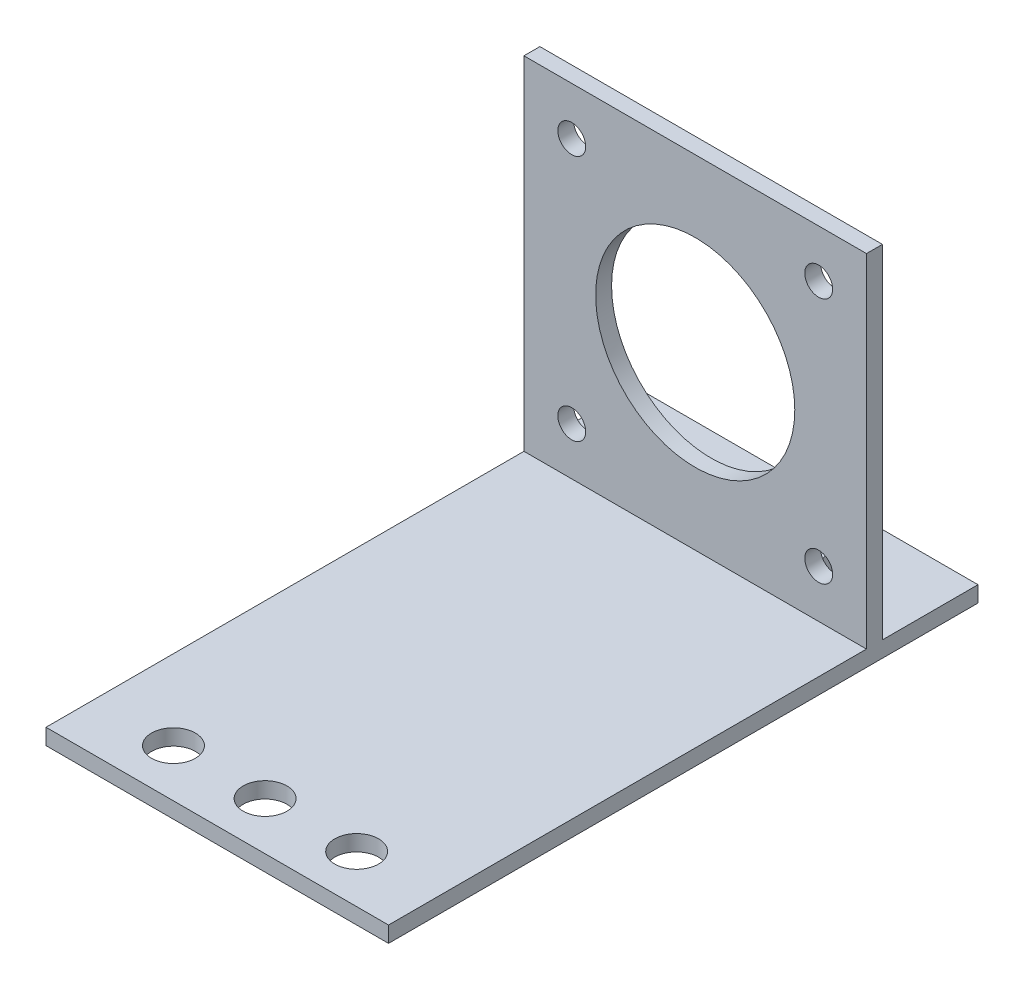
SolidWorks part; units mm, degrees
ref_plane "Front Plane" through (0, 0, 0) normal (0, 0, 1) x (1, 0, 0)
ref_plane "Top Plane" through (0, 0, 0) normal (0, 1, 0) x (1, 0, 0)
ref_plane "Right Plane" through (0, 0, 0) normal (1, 0, 0) x (0, 0, -1)
sketch "Sketch1" plane through (0, 0, 0) normal (0, 1, 0) x (1, 0, 0)
  line L0 (-21.5, 25) -> (21.5, 25)
  line L1 (-21.5, -37) -> (21.5, -37)
  line L2 (-21.5, -37) -> (-21.5, 37)
  line L3 (-21.5, 37) -> (21.5, 37)
  line L4 (21.5, -37) -> (21.5, 37)
  line L5 (-21.5, -37) -> (21.5, 37) construction
  line L6 (-21.5, 37) -> (21.5, -37) construction
  line L7 (-21.5, 23) -> (21.5, 23)
  line L8 (21.5, -25) -> (-21.5, -25) construction
  line L9 (0, 37) -> (0, -37) construction
  circle A0 centre (0, 31) radius 2.75
  circle A1 centre (0, -31) radius 2.75
  point P0 (0, 0)
  dimension "D6" = 6
  dimension "D7" = 5.5
  dimension "D8" = 5.5
  dimension "D9" = 6
  dimension "D1" = 12
  dimension "D2" = 2
  dimension "D3" = 43
  dimension "D4" = 48
  dimension "D5" = 12
extrude "Boss-Extrude1" add sketch "Sketch1" along normal blind 43 contours L2 L7 L4 L0 region at (0, 0, -24)
extrude "Boss-Extrude2" add sketch "Sketch1<3>" against normal blind 2 contours L4 L3 L2 L1
sketch "Sketch1<3>" plane through (0, 0, 0) normal (0, 1, 0) x (1, 0, 0) same geometry as "Sketch1"
sketch "Sketch2" plane through (0, 0, -23) normal (0, 0, 1) x (1, 0, 0)
  line L0 (-21.5, 43) -> (21.5, 43) construction
  line L1 (-15.5, 6) -> (15.5, 6) construction
  line L2 (-15.5, 6) -> (-15.5, 37) construction
  line L3 (-15.5, 37) -> (15.5, 37) construction
  line L4 (15.5, 6) -> (15.5, 37) construction
  line L5 (-15.5, 6) -> (15.5, 37) construction
  line L6 (-15.5, 37) -> (15.5, 6) construction
  line L7 (-21.5, 43) -> (-21.5, 0) construction
  line L8 (21.5, 43) -> (21.5, 0) construction
  line L9 (-21.5, 0) -> (21.5, 0) construction
  circle A0 centre (0, 21.5) radius 12.5
  circle A1 centre (-15.5, 37) radius 1.75
  circle A2 centre (15.5, 37) radius 1.75
  circle A3 centre (15.5, 6) radius 1.75
  circle A4 centre (-15.5, 6) radius 1.75
  point P0 (0, 21.5)
  point P25 (0, 21.5)
  point P26 (0, 21.5)
  dimension "D5" = 4
  dimension "D1" = 6
  dimension "D2" = 6
  dimension "D3" = 6
  dimension "D4" = 6
extrude "Cut-Extrude1" cut sketch "Sketch2" against normal up to next contours A0 | A1 | A3 | A4 | A2
extrude "Cut-Extrude2" cut sketch "Sketch1<4>" against normal up to next contours A0 | A1 region at (0, 0, -31) region at (0, 0, 31)
sketch "Sketch1<4>" plane through (0, 0, 0) normal (0, 1, 0) x (1, 0, 0) same geometry as "Sketch1"
pattern_linear "LPattern1" count 2 spacing 11.5 along (1, 0, 0) count 2 spacing 11.5 along (-1, 0, 0) of "Cut-Extrude2" pattern seed only yes
